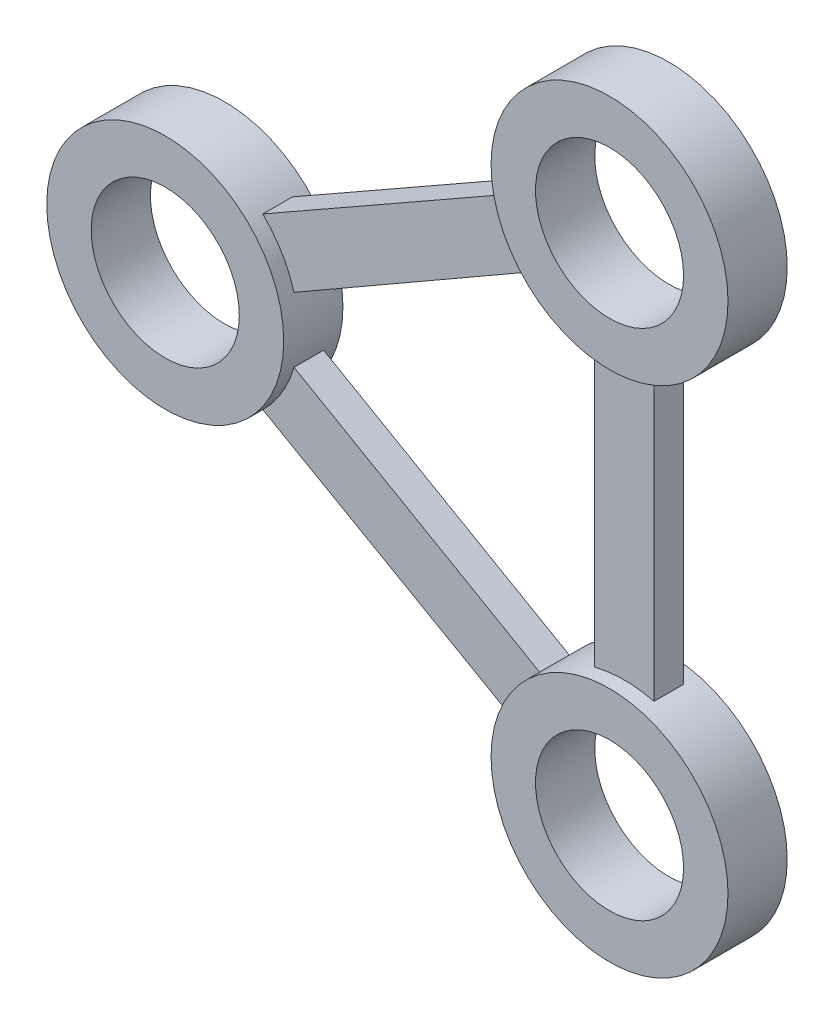
SolidWorks part; units mm, degrees
ref_plane "Front Plane" through (0, 0, 0) normal (0, 0, 1) x (1, 0, 0)
ref_plane "Top Plane" through (0, 0, 0) normal (0, 1, 0) x (1, 0, 0)
ref_plane "Right Plane" through (0, 0, 0) normal (1, 0, 0) x (0, 0, -1)
sketch "Sketch1" plane through (0, 0, 0) normal (0, 0, 1) x (1, 0, 0)
  line L0 (0, 86.6) -> (0, -86.6) construction
  line L1 (10, 47.8702) -> (10, -47.8702)
  line L2 (-10, 47.8702) -> (-10, -47.8702)
  line L3 (0, -86.6) -> (-150, 0) construction
  line L4 (-150, 0) -> (0, 86.6) construction
  line L5 (-122.0497, 28.6144) -> (-38.6045, 76.1266)
  line L6 (-111.5286, 10.9523) -> (-28.5934, 58.6283)
  line L7 (-270.0133, 0) -> (249.5775, 0) construction
  line L8 (-111.5286, -10.9523) -> (-28.5934, -58.6283)
  line L9 (-122.0497, -28.6144) -> (-38.6045, -76.1266)
  circle A0 centre (0, 86.6) radius 25
  circle A1 centre (0, -86.6) radius 25
  circle A2 centre (0, 86.6) radius 40
  circle A3 centre (0, -86.6) radius 40
  circle A4 centre (-150, 0) radius 40
  circle A5 centre (-150, 0) radius 25
  arc A6 (-111.5286, 10.9523) -> (-122.0497, 28.6144) centre (-150, 0) ccw
  arc A7 (-28.5934, 58.6283) -> (-38.6045, 76.1266) centre (0, 86.6) cw
  arc A8 (-122.0497, -28.6144) -> (-111.5286, -10.9523) centre (-150, 0) ccw
  arc A9 (-38.6045, -76.1266) -> (-28.5934, -58.6283) centre (0, -86.6) cw
  arc A10 (-10, -47.8702) -> (10, -47.8702) centre (0, -86.6) cw
  arc A11 (-10, 47.8702) -> (10, 47.8702) centre (0, 86.6) ccw
  dimension "D1" = 80
  dimension "D2" = 80
  dimension "D3" = 80
  dimension "D4" = 50
  dimension "D5" = 50
  dimension "D6" = 50
  dimension "D7" = 150
  dimension "D8" = 173.2
  dimension "D9" = 86.6
  dimension "D10" = 86.6
  dimension "D11" = 10
  dimension "D12" = 10
  dimension "D13" = 10
extrude "Boss-Extrude1" add sketch "Sketch1" along normal blind 5 and the other way blind 5 contours A7 L5 A6 L6 | A11 L1 A10 L2 | A9 L8 A8 L9
extrude "Boss-Extrude2" add sketch "Sketch1<6>" along normal blind 10 and the other way blind 10 contours A5 | A4 | A2 | A0 | A3 | A1
sketch "Sketch1<6>" plane through (0, 0, 0) normal (0, 0, 1) x (1, 0, 0) same geometry as "Sketch1"
